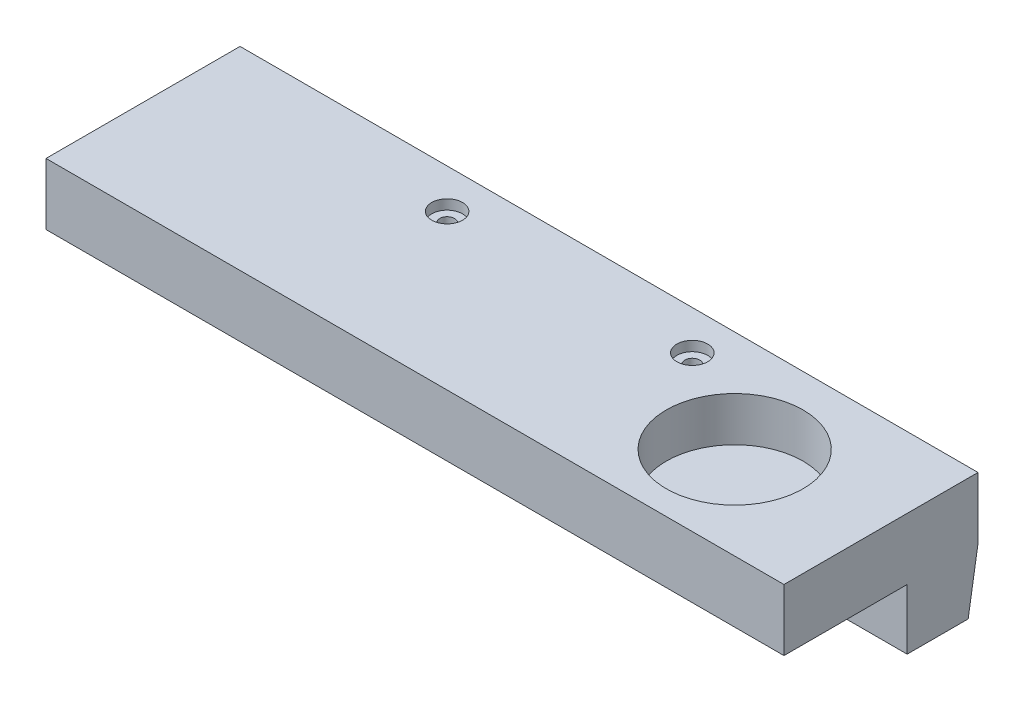
SolidWorks part; units mm, degrees
ref_plane "Płaszczyzna przednia" through (0, 0, 0) normal (0, 0, 1) x (1, 0, 0)
ref_plane "Płaszczyzna górna" through (0, 0, 0) normal (0, 1, 0) x (1, 0, 0)
ref_plane "Płaszczyzna prawa" through (0, 0, 0) normal (1, 0, 0) x (0, 0, -1)
sketch "Szkic1" plane through (0, 0, 0) normal (0, 0, 1) x (1, 0, 0)
  line L1 (-58.3066, 32.0248) -> (61.4934, 32.0248)
  line L2 (-58.3066, 32.0248) -> (-58.3066, 22.0248)
  line L3 (-58.3066, 22.0248) -> (61.4934, 22.0248)
  line L4 (61.4934, 32.0248) -> (61.4934, 22.0248)
  dimension "D1" = 119.8
  dimension "D2" = 10
extrude "Dodanie-wyciągnięcie2" add sketch "Szkic1" along normal blind 30 contours L2 L3 L4 L1
sketch "Szkic21" plane through (0, 32.0248, 0) normal (0, 1, 0) x (1, 0, 0)
  line L0 (61.4934, -30) -> (61.4934, 0) construction
  line L1 (-58.3066, 0) -> (61.4934, 0)
  line L2 (-58.3066, 0) -> (-58.3066, -10)
  line L3 (-58.3066, -10) -> (61.4934, -10)
  line L4 (61.4934, 0) -> (61.4934, -10)
extrude "Dodanie-wyciągnięcie3" add sketch "Szkic21" along normal blind 9.8
sketch "Szkic22" plane through (0, 22.0248, 0) normal (0, -1, 0) x (1, 0, 0)
  line L0 (-58.3066, 4.88) -> (-18.3066, 4.88) construction
  line L1 (-58.3066, 30) -> (-58.3066, 0) construction
  line L2 (-18.3066, 4.88) -> (21.4934, 4.88) construction
  line L3 (21.4934, 4.88) -> (61.4934, 4.88) construction
  line L4 (61.4934, 30) -> (61.4934, 0) construction
  line L5 (1.9729, 4.88) -> (1.9729, 0) construction
  line L6 (-58.3066, 0) -> (61.4934, 0) construction
hole_wizard "Pogłębienie walcowe pod M2 wkręt do części metalowych z łbem stożkowym ściętym2" positions "Szkic23" profile "Szkic24" counterbore size "M2" standard "Ansi Metric" end condition through all
sketch "Szkic23" plane through (0, 22.0248, 0) normal (0, -1, 0) x (-1, 0, 0)
  point P0 (-21.4934, -4.88)
  point P3 (18.3066, -4.88)
sketch "Szkic24" plane through (21.4934, 22.0248, 4.88) normal (1, 0, 0) x (0, 0, -1)
  line L0 (0, 0) -> (0, 19.8)
  line L1 (0, 19.8) -> (1.2, 19.8)
  line L3 (1.2, 19.8) -> (1.2, 1.6)
  line L4 (1.2, 1.6) -> (2.5, 1.6)
  line L5 (2.5, 1.6) -> (2.5, 0)
  line L7 (2.5, 0) -> (0, 0)
  line L11 (0, -6.35) -> (0, 107.95) construction
  dimension "Średnica otworu na wylot" = 2.4
  dimension "Głębokość otworu na wylot" = 19.8
  dimension "Średnica pogłębienia walcowego" = 5
  dimension "Głębokość pogłębienia walcowego" = 1.6
sketch "Szkic28" plane through (0, 22.0248, 0) normal (0, -1, 0) x (1, 0, 0)
  line L0 (38.4934, 0) -> (38.4934, 15) construction
  line L1 (-58.3066, 0) -> (61.4934, 0) construction
  line L2 (38.4934, 15) -> (61.4934, 15) construction
  line L3 (61.4934, 30) -> (61.4934, 0) construction
  line L4 (-58.3066, 30) -> (61.4934, 30) construction
  circle A0 centre (38.4934, 15) radius 11.1
  dimension "D1" = 15
extrude "Wytnij-wyciągnięcie1" cut sketch "Szkic28" against normal blind 7.2
sketch "Szkic31" plane through (61.4934, 0, 0) normal (1, 0, 0) x (0, 0, -1)
  line L0 (-10, 32.0248) -> (-10, 71.9248)
  line L2 (0, 41.2325) -> (0, 32.0248)
  line L6 (0, 41.8248) -> (0, 22.0248) construction
  line L8 (0, 32.0248) -> (1.5, 32.0248)
  line L10 (-10, 32.0248) -> (1.5, 32.0248)
  line L12 (-10, 71.9248) -> (-5, 71.9248)
  line L13 (-5, 71.9248) -> (1.5, 32.0248)
  line L14 (-0.4105, 43.7521) -> (0.2752, 39.543)
  line L15 (0.2752, 39.543) -> (3.3905, 40.0505)
  line L16 (3.3905, 40.0505) -> (-0.4105, 43.7521)
  line M5 (0, 22.0248) -> (0, 41.8248)
  line M6 (0, 41.8248) -> (-10, 41.8248)
extrude "Wytnij-wyciągnięcie4" cut sketch "Szkic31" against normal blind 124.8 contours L13 M6 M5 region at (61.4934, 41.6274, 0.0322)
extrude "Dodanie-wyciągnięcie5" add sketch "Szkic31<5>" against normal blind 119.8 contours L13 L8 M5 region at (61.4934, 35.0941, -0.5)
sketch "Szkic31<5>" plane through (61.4934, 0, 0) normal (1, 0, 0) x (0, 0, -1) same geometry as "Szkic31"
sketch "Szkic34" plane through (0, 0, 0) normal (0, 0, -1) x (-1, 0, 0)
  line L1 (-61.4934, 32.0248) -> (58.3066, 32.0248)
  line L2 (-61.4934, 32.0248) -> (-61.4934, 22.0248)
  line L3 (-61.4934, 22.0248) -> (58.3066, 22.0248)
  line L4 (58.3066, 32.0248) -> (58.3066, 22.0248)
extrude "Dodanie-wyciągnięcie6" add sketch "Szkic34" along normal blind 1.5
mirror "Lustro2" about plane through (-58.3066, 22.0248, 30) normal (0, 1, 0) of bodies 125 126
move or copy body "Obiekt-Przenieś/Kopiuj1" bodies to move or copy 145 copy no translate (0, -41, 0) parameters "D1"=0, "D2"=41, "D3"=0
delete or keep bodies "Obiekt-Usuń/zachowaj 1" type delete bodies bodies 125
